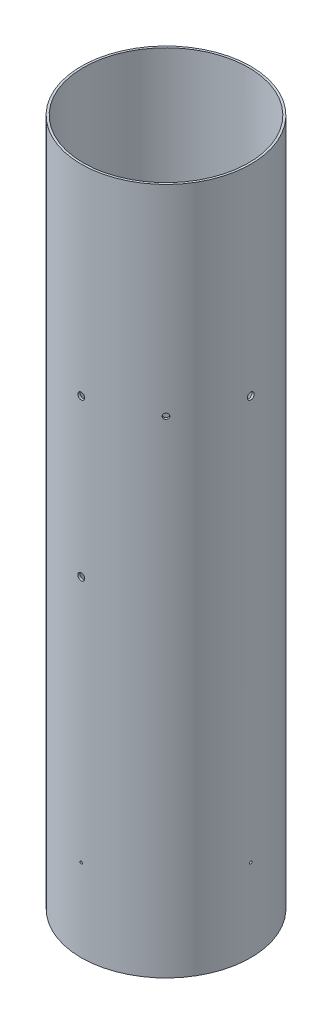
SolidWorks part; units mm, degrees
material "C-Glass Fiber"
ref_plane "Front Plane" through (0, 0, 0) normal (0, 0, 1) x (1, 0, 0)
ref_plane "Top Plane" through (0, 0, 0) normal (0, 1, 0) x (1, 0, 0)
ref_plane "Right Plane" through (0, 0, 0) normal (1, 0, 0) x (0, 0, -1)
sketch "Sketch2" plane through (0, 0, 0) normal (0, 1, 0) x (1, 0, 0)
  circle A0 centre (0, 0) radius 76.3651
  circle A1 centre (0, 0) radius 78.359
  dimension "D1" = 152.7302
  dimension "D2" = 156.718
extrude "Boss-Extrude1" add sketch "Sketch2" along normal blind 635
sketch "Sketch3" plane through (0, 0, 0) normal (0, 0, 1) x (1, 0, 0)
  circle A0 centre (0, 76.2) radius 1.1906
  dimension "D2" = 2.3813
  dimension "D1" = 76.2
extrude "Cut-Extrude1" cut sketch "Sketch3" against normal through all both and the other way through all
pattern_circular "CirPattern1" count 4 over 360 about axis through (0, 635, 0) along (0, 1, 0) of "Cut-Extrude1"
sketch "Sketch4" plane through (0, 0, 0) normal (0, 0, 1) x (1, 0, 0)
  circle A0 centre (0, 449.5038) radius 3.175
  dimension "D2" = 6.35
  dimension "D1" = 449.5038
extrude "Cut-Extrude2" cut sketch "Sketch4" against normal through all both and the other way through all
pattern_circular "CirPattern2" count 4 over 360 about axis through (0, 635, 0) along (0, 1, 0) of "Cut-Extrude2"
ref_plane "Plane1" through (55.4082, 0, 55.4082) normal (0.7071, 0, 0.7071) x (0, -1, 0)
sketch "Sketch5" plane through (55.4082, 0, 55.4082) normal (0.7071, 0, 0.7071) x (0, -1, 0)
  circle A0 centre (-449.5038, 0) radius 2.5019
  dimension "D1" = 5.0038
  dimension "D2" = 449.5038
extrude "Cut-Extrude3" cut sketch "Sketch5" against normal up to surface and the other way through all up to face at (-76.3025, 448.7766, 3.0906)
sketch "Sketch6" plane through (0, 0, 0) normal (0, 0, 1) x (1, 0, 0)
  circle A0 centre (0, 304.8) radius 3.175
  dimension "D2" = 304.8
extrude "Cut-Extrude4" cut sketch "Sketch6" against normal through all both and the other way through all
equation "\"Shear Pin Dia\"= 3 / 32"
equation "\"Shear Pin Offset\"= 3"
equation "\"D1@Sketch3\"=\"Shear Pin Offset\""
equation "\"D2@Sketch3\"=\"Shear Pin Dia\""
equation "\"Bulkhead Screw Dia\"= 1 / 4"
equation "\"Bulkhead Screw Offset\"= 17.697"
equation "\"D1@Sketch4\"=\"Bulkhead Screw Offset\""
equation "\"D2@Sketch4\"=\"Bulkhead Screw Dia\""
equation "\"Rail Button Offset\"= 17.697"
equation "\"Rail Button Dia\"= 0.197"
equation "\"D1@Sketch5\"=\"Rail Button Dia\""
equation "\"Vent Hole Dia\"= 0.25"
equation "\"Vent Hole Offset\"= 12"
equation "\"D2@Sketch6\"=\"Vent Hole Offset\""
